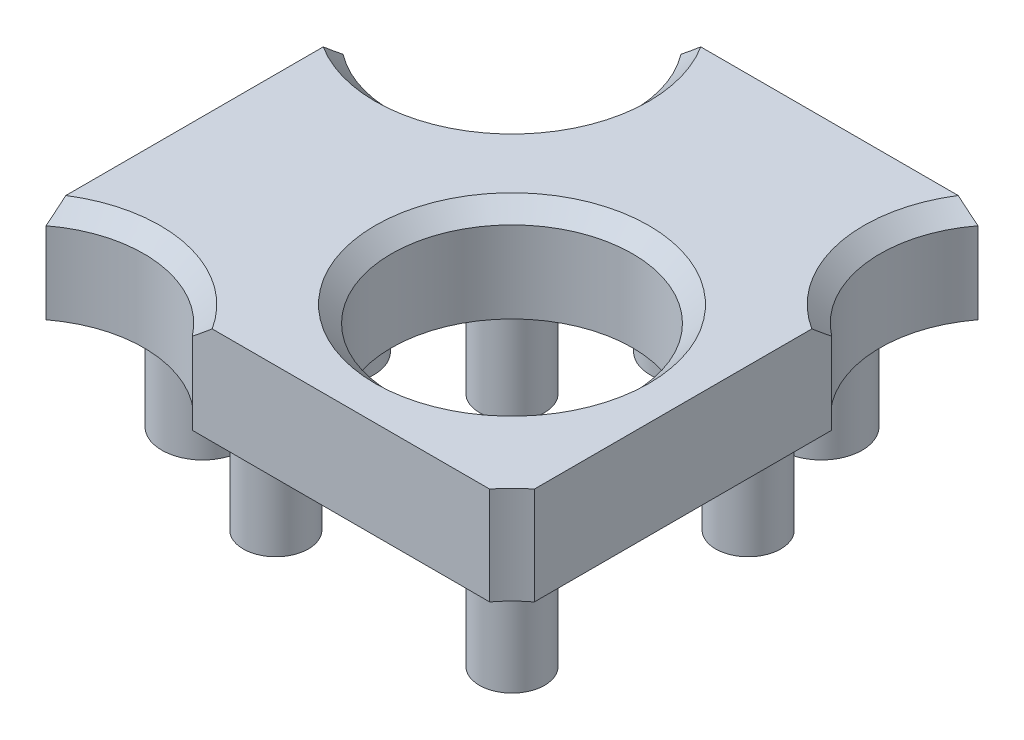
SolidWorks part; units mm, degrees
ref_plane "Front Plane" through (0, 0, 0) normal (0, 0, 1) x (1, 0, 0)
ref_plane "Top Plane" through (0, 0, 0) normal (0, 1, 0) x (1, 0, 0)
ref_plane "Right Plane" through (0, 0, 0) normal (1, 0, 0) x (0, 0, -1)
sketch "Sketch1" plane through (0, 0, 0) normal (0, 1, 0) x (1, 0, 0)
  line L1 (-10.5, -10.5) -> (10.5, -10.5)
  line L2 (-10.5, -10.5) -> (-10.5, 10.5)
  line L3 (-10.5, 10.5) -> (10.5, 10.5)
  line L4 (10.5, -10.5) -> (10.5, 10.5)
  line L5 (-10.5, -10.5) -> (10.5, 10.5) construction
  line L6 (-10.5, 10.5) -> (10.5, -10.5) construction
  point P0 (0, 0)
  dimension "D1" = 21
  dimension "D2" = 21
extrude "Boss-Extrude1" add sketch "Sketch1" along normal blind 12
sketch "Sketch2" plane through (0, 12, 0) normal (0, 1, 0) x (1, 0, 0)
  circle A0 centre (0, 0) radius 7.4
  dimension "D1" = 14.8
extrude "Cut-Extrude1" cut sketch "Sketch2" against normal up to next
sketch "Sketch3" plane through (0, 0, 10.5) normal (0, 0, 1) x (1, 0, 0)
  line L0 (16.4945, 0) -> (-16.4945, 0) construction
  line L1 (-10.5, 0) -> (10.5, 0)
  line L2 (-10.5, 0) -> (-10.5, 6)
  line L3 (-10.5, 6) -> (10.5, 6)
  line L4 (10.5, 0) -> (10.5, 6)
  line L5 (10.5, 12) -> (10.5, 0) construction
  line L6 (-10.5, 12) -> (-10.5, 0) construction
extrude "Boss-Extrude2" add sketch "Sketch3" along normal blind 8.99
sketch "Sketch4" plane through (0, 0, -10.5) normal (0, 0, -1) x (-1, 0, 0)
  line L0 (10.5, 12) -> (10.5, 0) construction
  line L1 (-10.5, 12) -> (10.5, 12)
  line L2 (-10.5, 12) -> (-10.5, 6)
  line L3 (-10.5, 6) -> (10.5, 6)
  line L4 (10.5, 12) -> (10.5, 6)
extrude "Boss-Extrude3" add sketch "Sketch4" along normal blind 8.99
sketch "Sketch5" plane through (0, 6, 0) normal (0, -1, 0) x (1, 0, 0)
  line L0 (0, -6.6) -> (0, 6.6) construction
  line L1 (10.5, -10.5) -> (-10.5, -10.5) construction
  line L2 (-2.5, -10.5) -> (10.5, -19.49) construction
  circle A0 centre (4, -14.995) radius 2.5
  dimension "D1" = 5
  dimension "D2" = 2.5
extrude "Boss-Extrude4" add sketch "Sketch5" along normal blind 6
sketch "Sketch6" plane through (0, 6, 0) normal (0, 1, 0) x (1, 0, 0)
  line L0 (10.5, -19.49) -> (-10.5, -19.49) construction
  line L2 (-1.5, -19.49) -> (10.5, -10.5) construction
  line L3 (0, -6.6) -> (0, 6.6) construction
  circle A0 centre (4.5, -14.995) radius 2.6
  dimension "D1" = 5.2
  dimension "D2" = 1.5
extrude "Cut-Extrude2" cut sketch "Sketch6" against normal up to next
ref_axis "Axis1" through (0, 0, 0) along (0, 1, 0)
mirror "Mirror1" about plane through (0, 0, 0) normal (1, 0, 0) of "Boss-Extrude4"
mirror "Mirror2" about plane through (0, 0, 0) normal (1, 0, 0) of "Cut-Extrude2"
pattern_circular "CirPattern1" count 2 every 90 about axis through (0, 0, 0) along (0, 1, 0) of "Boss-Extrude2", "Boss-Extrude3", "Boss-Extrude4", "Cut-Extrude2", "Mirror1", "Mirror2"
sketch "Sketch7" plane through (0, 6, 0) normal (0, -1, 0) x (1, 0, 0)
  line L1 (-10.5, -10.5) -> (21.1591, -10.5)
  line L2 (-10.5, -10.5) -> (-10.5, 20.9698)
  line L3 (-10.5, 20.9698) -> (21.1591, 20.9698)
  line L4 (21.1591, -10.5) -> (21.1591, 20.9698)
extrude "Cut-Extrude3" cut sketch "Sketch7" along normal blind 11
fillet "Fillet1" radius 7 1 edges at (-10.5, 9, -10.5)
sketch "Sketch9" plane through (0, 12, 0) normal (0, 1, 0) x (1, 0, 0)
  line L0 (0, 0) -> (-30, 30) construction
  circle A0 centre (-15, 15) radius 7.4
  dimension "D3" = 14.8
  dimension "D1" = 30
  dimension "D2" = 30
extrude "Cut-Extrude4" cut sketch "Sketch9" against normal blind 11
pattern_circular "CirPattern2" count 4 over 360 about axis through (0, -0.001, 0) along (0, 1, 0) of "Cut-Extrude4" reverse direction yes
sketch "Sketch10" plane through (0, 6, 0) normal (0, -1, 0) x (1, 0, 0)
  line L0 (0, 0) -> (-7.25, 7.25) construction
  circle A0 centre (-7.25, 7.25) radius 2
  dimension "D1" = 4
extrude "Boss-Extrude5" add sketch "Sketch10" along normal up to surface (6 mm away)
pattern_circular "CirPattern3" count 4 over 360 about axis through (0, -0.001, 0) along (0, 1, 0) of "Boss-Extrude5" reverse direction yes
chamfer "Chamfer1" distance 1 angle 45 1 edges at (0, 12, 7.4)
chamfer "Chamfer2" distance 1 angle 45 3 edges at (-14.0218, 12, 7.6649) (7.6649, 12, -14.0218) (-9.7674, 12, -9.7674)
